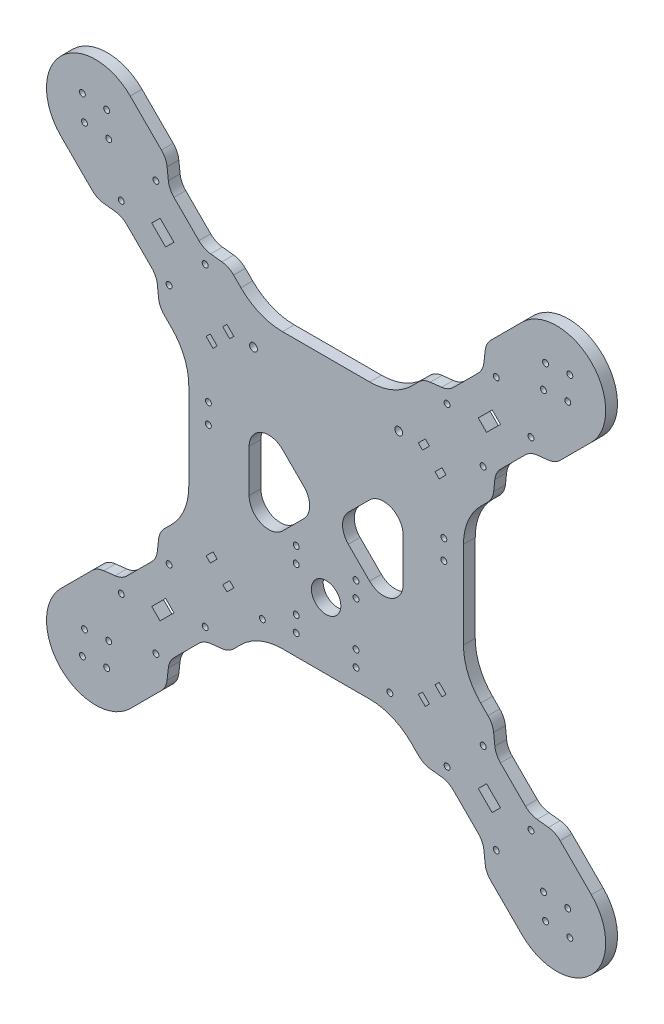
SolidWorks part; units mm, degrees
ref_plane "Front Plane" through (0, 0, 0) normal (0, 0, 1) x (1, 0, 0)
ref_plane "Top Plane" through (0, 0, 0) normal (0, 1, 0) x (1, 0, 0)
ref_plane "Right Plane" through (0, 0, 0) normal (1, 0, 0) x (0, 0, -1)
sketch "Sketch4" plane through (0, 0, 0) normal (0, 0, 1) x (1, 0, 0)
  line L0 (-117.5, 117.5) -> (117.5, -117.5) construction
  line L1 (-117.5, -117.5) -> (117.5, 117.5) construction
  line L2 (-1000, 0) -> (49000, 0) construction
  line L3 (0, -1000) -> (0, 49000) construction
  line L4 (-70, -34.6447) -> (-70, 34.6447)
  line L5 (34.6447, 70) -> (-34.6447, 70)
  line L6 (-70, 34.6447) -> (-135.1777, 99.8223)
  line L7 (-34.6447, 70) -> (-99.8223, 135.1777)
  line L8 (-135.1777, 99.8223) -> (-99.8223, 135.1777) construction
  line L9 (70, -34.6447) -> (70, 34.6447)
  line L10 (70, 34.6447) -> (135.1777, 99.8223)
  line L11 (34.6447, 70) -> (99.8223, 135.1777)
  line L12 (70, -34.6447) -> (135.1777, -99.8223)
  line L13 (34.6447, -70) -> (99.8223, -135.1777)
  line L14 (34.6447, -70) -> (-34.6447, -70)
  line L15 (-34.6447, -70) -> (-99.8223, -135.1777)
  line L16 (-70, -34.6447) -> (-135.1777, -99.8223)
  line L17 (-124.5711, 89.2157) -> (-89.2157, 124.5711) construction
  line L18 (-120.3284, 84.9731) -> (-84.9731, 120.3284) construction
  arc A0 (-135.1777, 99.8223) -> (-99.8223, 135.1777) centre (-117.5, 117.5) cw
  arc A1 (135.1777, 99.8223) -> (99.8223, 135.1777) centre (117.5, 117.5) ccw
  arc A2 (135.1777, -99.8223) -> (99.8223, -135.1777) centre (117.5, -117.5) cw
  arc A3 (-135.1777, -99.8223) -> (-99.8223, -135.1777) centre (-117.5, -117.5) ccw
  point P13 (-117.5, 117.5)
  point P17 (-135.1777, 135.1777)
  point P19 (0, 70)
  point P24 (70, 0)
  point P31 (-70, 0)
  dimension "D6" = 40
  dimension "D1" = 235
  dimension "D2" = 235
  dimension "D3" = 70
  dimension "D4" = 70
  dimension "D5" = 50
  dimension "D7" = 6
extrude "Boss-Extrude1" add sketch "Sketch4" along normal blind 6
fillet "Fillet1" radius 30 8 edges at (34.6447, -70, 3) (70, -34.6447, 3) (70, 34.6447, 3) (34.6447, 70, 3) (-34.6447, 70, 3) (-70, 34.6447, 3) (-70, -34.6447, 3) (-34.6447, -70, 3)
sketch "Sketch8" plane through (0, 0, 6) normal (0, 0, 1) x (1, 0, 0)
  line L0 (-120.3284, 84.9731) -> (-84.9731, 120.3284) construction
  line L1 (-117.5, 117.5) -> (117.5, -117.5) construction
  line L2 (-88.8622, 84.6195) -> (-84.6195, 88.8622)
  line L3 (-88.8622, 84.6195) -> (-81.7911, 77.5485)
  line L4 (-84.6195, 88.8622) -> (-77.5485, 81.7911)
  line L5 (-81.7911, 77.5485) -> (-77.5485, 81.7911)
  circle A0 centre (-104.4185, 86.7409) radius 1.5
  circle A2 centre (-80.0233, 61.6386) radius 1.5
  circle A4 centre (-86.7409, 104.4185) radius 1.5
  circle A5 centre (-61.6386, 80.0233) radius 1.5
  dimension "D1" = 3
  dimension "D2" = 10
  dimension "D3" = 12.5
  dimension "D4" = 13
  dimension "D5" = 45
  dimension "D6" = 10
  dimension "D7" = 12.5
  dimension "D8" = 45
  dimension "D9" = 13
  dimension "D10" = 6
  dimension "D11" = 3
  dimension "D12" = 22.5
  dimension "D13" = 10
sketch "Sketch9" plane through (0, 0, 6) normal (0, 0, 1) x (1, 0, 0)
  line L0 (-135.1777, 99.8223) -> (-99.8223, 135.1777) construction
  line L1 (-117.5, 117.5) -> (117.5, -117.5) construction
  circle A0 centre (-124.2175, 124.2175) radius 1.5
  circle A1 centre (-110.7825, 110.7825) radius 1.5
  circle A2 centre (-123.1569, 111.8431) radius 1.5
  circle A3 centre (-111.8431, 123.1569) radius 1.5
  dimension "D5" = 3
  dimension "D1" = 8
  dimension "D2" = 8
  dimension "D3" = 9.5
  dimension "D4" = 9.5
extrude "Cut-Extrude1" cut sketch "Sketch8" against normal through all both and the other way through all
extrude "Cut-Extrude2" cut sketch "Sketch9" against normal through all both and the other way through all
mirror "Mirror1" about plane through (0, 0, 0) normal (1, 0, 0) of "Cut-Extrude2", "Cut-Extrude1"
mirror "Mirror2" about plane through (0, 0, 0) normal (0, 1, 0) of "Mirror1"
sketch "Sketch10" plane through (0, 0, 6) normal (0, 0, 1) x (1, 0, 0)
  line L0 (-70, -34.6447) -> (-70, 34.6447) construction
  line L1 (70, -34.6447) -> (70, 34.6447) construction
  line L2 (34.6447, 70) -> (-34.6447, 70) construction
  line L3 (-49.1421, -53.3848) -> (-47.0208, -55.5061)
  line L4 (0, -201000) -> (0, 249000) construction
  line L5 (-201000, 0) -> (249000, 0) construction
  line L6 (-4.2426, 0) -> (-39.2426, 35)
  line L7 (-39.2426, 35) -> (-39.2426, -35)
  line L8 (-39.2426, -35) -> (-4.2426, 0)
  line L9 (-117.5, 117.5) -> (117.5, -117.5) construction
  line L10 (-117.5, -117.5) -> (117.5, 117.5) construction
  line L11 (0, -3.3) -> (0, 3.3) construction
  line L12 (39.2426, 35) -> (39.2426, -35)
  line L13 (4.2426, 0) -> (39.2426, 35)
  line L14 (39.2426, -35) -> (4.2426, 0)
  line L21 (3.3, 0) -> (-3.3, 0) construction
  line L22 (-57.6274, -44.8995) -> (-55.5061, -47.0208)
  line L23 (-59.0416, -50.5563) -> (-55.5061, -47.0208)
  line L24 (-61.163, -48.435) -> (-59.0416, -50.5563)
  line L25 (-61.163, 48.435) -> (-59.0416, 50.5563)
  line L26 (-61.163, 48.435) -> (-57.6274, 44.8995)
  line L27 (-57.6274, 44.8995) -> (-55.5061, 47.0208)
  line L28 (-59.0416, 50.5563) -> (-55.5061, 47.0208)
  line L29 (-61.163, -48.435) -> (-57.6274, -44.8995)
  line L30 (57.6274, 44.8995) -> (55.5061, 47.0208)
  line L31 (59.0416, 50.5563) -> (55.5061, 47.0208)
  line L32 (61.163, 48.435) -> (59.0416, 50.5563)
  line L33 (61.163, 48.435) -> (57.6274, 44.8995)
  line L34 (61.163, -48.435) -> (57.6274, -44.8995)
  line L35 (61.163, -48.435) -> (59.0416, -50.5563)
  line L36 (59.0416, -50.5563) -> (55.5061, -47.0208)
  line L37 (57.6274, -44.8995) -> (55.5061, -47.0208)
  line L38 (-52.6777, 56.9203) -> (-50.5563, 59.0416)
  line L39 (-52.6777, 56.9203) -> (-49.1421, 53.3848)
  line L40 (-49.1421, 53.3848) -> (-47.0208, 55.5061)
  line L41 (-50.5563, 59.0416) -> (-47.0208, 55.5061)
  line L42 (-50.5563, -59.0416) -> (-47.0208, -55.5061)
  line L43 (-52.6777, -56.9203) -> (-50.5563, -59.0416)
  line L44 (-52.6777, -56.9203) -> (-49.1421, -53.3848)
  line L45 (52.6777, -56.9203) -> (49.1421, -53.3848)
  line L46 (52.6777, -56.9203) -> (50.5563, -59.0416)
  line L47 (50.5563, -59.0416) -> (47.0208, -55.5061)
  line L48 (49.1421, -53.3848) -> (47.0208, -55.5061)
  line L49 (49.1421, 53.3848) -> (47.0208, 55.5061)
  line L50 (50.5563, 59.0416) -> (47.0208, 55.5061)
  line L51 (52.6777, 56.9203) -> (50.5563, 59.0416)
  line L52 (52.6777, 56.9203) -> (49.1421, 53.3848)
  line L53 (-15.25, -21) -> (15.25, -51.5) construction
  line L54 (-22.2183, -70) -> (22.2183, -70) construction
  circle A0 centre (-60, 20) radius 1.5
  circle A1 centre (-60, 10) radius 1.5
  circle A2 centre (60, 20) radius 1.5
  circle A3 centre (60, 10) radius 1.5
  circle A4 centre (-15.25, -21) radius 1.5
  circle A5 centre (15.25, -21) radius 1.5
  circle A6 centre (-15.25, -51.5) radius 1.5
  circle A7 centre (15.25, -51.5) radius 1.5
  circle A8 centre (0, -36.25) radius 7.5
  circle A9 centre (-37, 55.7426) radius 2
  circle A10 centre (37, 55.7426) radius 2
  circle A11 centre (32.5, -62) radius 1.5
  circle A12 centre (-32.5, -62) radius 1.5
  circle A13 centre (15.25, -29) radius 1.5
  circle A14 centre (-15.25, -29) radius 1.5
  circle A15 centre (15.25, -59.5) radius 1.5
  circle A16 centre (-15.25, -59.5) radius 1.5
  dimension "D2" = 10
  dimension "D5" = 3
  dimension "D8" = 3
  dimension "D17" = 15
  dimension "D18" = 3
  dimension "D19" = 3
  dimension "D1" = 10
  dimension "D3" = 10
  dimension "D4" = 50
  dimension "D6" = 30.5
  dimension "D7" = 30.5
  dimension "D9" = 15.25
  dimension "D10" = 21
  dimension "D11" = 3
  dimension "30" = 35
  dimension "D12" = 6
  dimension "D13" = 3
  dimension "D14" = 5
  dimension "D15" = 20
  dimension "D16" = 3
  dimension "D20" = 8
  dimension "D21" = 65
  dimension "D22" = 32.5
  dimension "D24" = 8
  dimension "D23" = 2
extrude "Cut-Extrude3" cut sketch "Sketch10" against normal through all both and the other way through all
fillet "Fillet2" radius 10 6 edges at (4.2426, 0, 3) (39.2426, -35, 3) (39.2426, 35, 3) (-39.2426, -35, 3) (-39.2426, 35, 3) (-4.2426, 0, 3)
sketch "Sketch11" plane through (0, 0, 6) normal (0, 0, 1) x (1, 0, 0)
  line L1 (-34.6447, 70) -> (-99.8223, 135.1777) construction
  line L2 (-80.0233, 104.065) -> (-62.3457, 86.3873)
  line L3 (-62.3457, 86.3873) -> (-49.6177, 84.9731)
  line L4 (-49.6177, 84.9731) -> (-81.4376, 116.7929)
  line L5 (-81.4376, 116.7929) -> (-80.0233, 104.065)
  line L6 (-80.0233, 104.065) -> (-74.3665, 109.7218) construction
  line L7 (-62.3457, 86.3873) -> (-56.6888, 92.0442) construction
  line L8 (-120.3284, 84.9731) -> (-84.9731, 120.3284) construction
  dimension "D1" = 45
  dimension "D2" = 8
  dimension "D3" = 10
  dimension "D4" = 10
  dimension "D5" = 5
extrude "Cut-Extrude4" cut sketch "Sketch11" against normal through all both and the other way through all
ref_plane "Plane1" through (0, 0, 0) normal (0.7071, 0.7071, 0) x (0.7071, -0.7071, 0)
mirror "Mirror4" about plane through (0, 0, 0) normal (0.7071, 0.7071, 0) of "Cut-Extrude4"
ref_axis "Axis1" through (0, 0, 0) along (0, 0, 1)
pattern_circular "CirPattern2" count 4 over 360 about axis through (0, 0, 0) along (0, 0, 1) of "Cut-Extrude4", "Mirror4"
fillet "Fillet3" radius 10 32 edges at (-49.6177, 84.9731, 3) (-62.3457, 86.3873, 3) (-80.0233, 104.065, 3) (-81.4376, 116.7929, 3) (116.7929, 81.4376, 3) (104.065, 80.0233, 3) (86.3873, 62.3457, 3) (84.9731, 49.6177, 3) (80.0233, 104.065, 3) (81.4376, 116.7929, 3) (62.3457, 86.3873, 3) (49.6177, 84.9731, 3) (116.7929, -81.4376, 3) (104.065, -80.0233, 3) (86.3873, -62.3457, 3) (84.9731, -49.6177, 3) (81.4376, -116.7929, 3) (80.0233, -104.065, 3) (62.3457, -86.3873, 3) (49.6177, -84.9731, 3) (-49.6177, -84.9731, 3) (-62.3457, -86.3873, 3) (-80.0233, -104.065, 3) (-81.4376, -116.7929, 3) (-116.7929, -81.4376, 3) (-104.065, -80.0233, 3) (-86.3873, -62.3457, 3) (-84.9731, -49.6177, 3) (-84.9731, 49.6177, 3) (-86.3873, 62.3457, 3) (-104.065, 80.0233, 3) (-116.7929, 81.4376, 3)
sketch "Sketch12" plane through (0, 0, 0) normal (0, 0, 1) x (1, 0, 0)
  line L0 (117.5, 117.5) -> (-117.5, -117.5) construction
  line L1 (-117.5, 117.5) -> (117.5, -117.5) construction
sketch "Sketch14" plane through (0, 0, 6) normal (0, 0, 1) x (1, 0, 0)
  line L6 (-15.25, -29) -> (15.25, -59.5) construction
  line L7 (-15.25, -59.5) -> (15.25, -29) construction
  line L13 (-17.25, -27) -> (17.25, -27) construction
  line L14 (-17.25, -27) -> (-17.25, -61.5) construction
  line L15 (-17.25, -61.5) -> (17.25, -61.5) construction
  line L16 (17.25, -27) -> (17.25, -61.5) construction
  line L17 (-17.25, -27) -> (17.25, -61.5) construction
  line L18 (-17.25, -61.5) -> (17.25, -27) construction
  point P4 (0, -44.25)
  point P5 (0, -44.25)
  dimension "D1" = 34.5
equation "\"D6@Sketch8\"=\"D2@Sketch8\""
equation "\"D7@Sketch8\"=\"D3@Sketch8\""
equation "\"D8@Sketch8\"=\"D5@Sketch8\""
equation "\"D9@Sketch8\"=\"D4@Sketch8\""
equation "\"D2@Sketch9\"=\"D1@Sketch9\""
equation "\"D4@Sketch9\"=\"D3@Sketch9\""
equation "\"D9@Sketch10\"=\"D6@Sketch10\"/2"
equation "\"D22@Sketch10\"= \"D21@Sketch10\" / 2"
